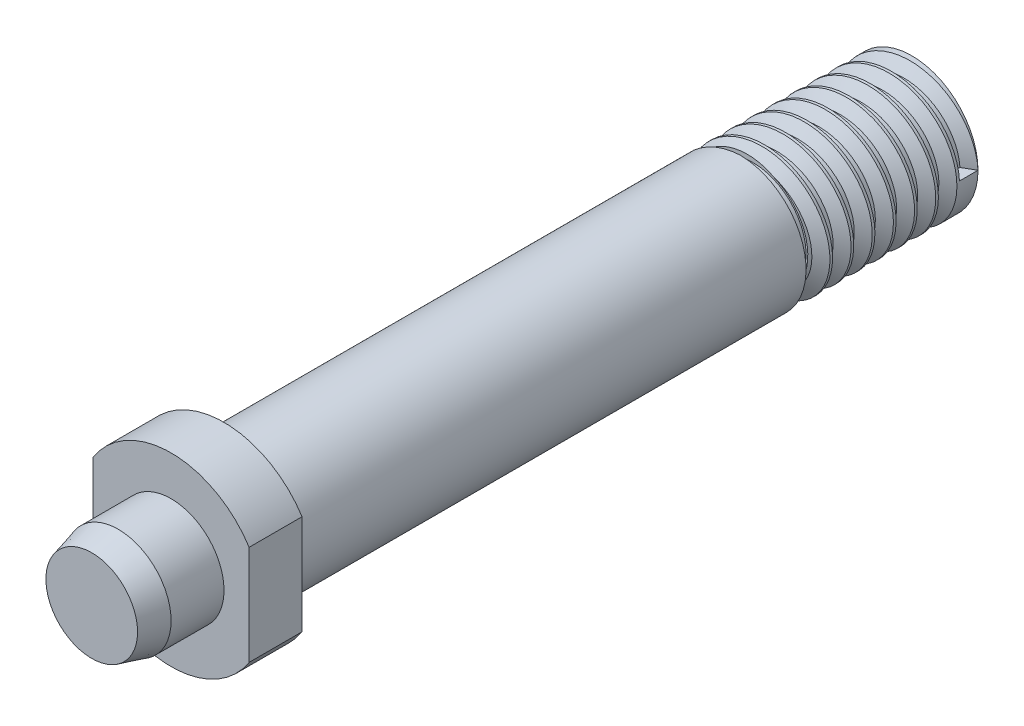
SolidWorks part; units mm, degrees
ref_plane "Front Plane" through (0, 0, 0) normal (0, 0, 1) x (1, 0, 0)
ref_plane "Top Plane" through (0, 0, 0) normal (0, 1, 0) x (1, 0, 0)
ref_plane "Right Plane" through (0, 0, 0) normal (1, 0, 0) x (0, 0, -1)
sketch "Sketch1" plane through (0, 0, 0) normal (0, 0, 1) x (1, 0, 0)
  circle A0 centre (0, 0) radius 2
  dimension "D1" = 4
extrude "Boss-Extrude1" add sketch "Sketch1" along normal blind 1 draft 15
sketch "Sketch2" plane through (0, 0, 0) normal (0, 0, -1) x (-1, 0, 0)
  circle A0 centre (0, 0) radius 2
extrude "Boss-Extrude2" add sketch "Sketch2" along normal blind 2
sketch "Sketch3" plane through (0, 0, -2) normal (0, 0, -1) x (-1, 0, 0)
  line L0 (-2.95, -1.8835) -> (-2.95, 1.8835)
  line L1 (2.95, -1.8835) -> (2.95, 1.8835)
  arc A0 (2.95, 1.8835) -> (-2.95, 1.8835) centre (0, 0) ccw
  arc A1 (-2.95, -1.8835) -> (2.95, -1.8835) centre (0, 0) ccw
  dimension "D1" = 7
  dimension "D2" = 5.9
extrude "Boss-Extrude3" add sketch "Sketch3" along normal blind 2
sketch "Sketch4" plane through (0, 0, -4) normal (0, 0, -1) x (-1, 0, 0)
  circle A0 centre (0, 0) radius 2.5
  dimension "D1" = 5
extrude "Boss-Extrude4" add sketch "Sketch4" along normal blind 19.5
sketch "Sketch5" plane through (0, 0, -23.5) normal (0, 0, -1) x (-1, 0, 0)
  circle A0 centre (0, 0) radius 2
  dimension "D1" = 4
extrude "Boss-Extrude5" add sketch "Sketch5" along normal blind 0.5
sketch "Sketch6" plane through (0, 0, -24) normal (0, 0, -1) x (-1, 0, 0)
  circle A0 centre (0, 0) radius 2.5
extrude "Boss-Extrude6" add sketch "Sketch6" along normal blind 6
thread "Thread1" pitch 0.8 method cut profile "Thread Profile1" start angle 0, offset 0, length 6, pitch 0.8, diameter 5
ref_plane "Plane1" through (2.5, 0, -30) normal (0, -1, 0) x (1, 0, 0)
sketch "Thread Profile1" plane through (2.5, 0, -30) normal (0, -1, 0) x (1, 0, 0)
  line L0 (0, 0) -> (0, 0.8) construction
  line L11 (0, 0) -> (0, 0.7)
  line L12 (0, 0.7) -> (-0.433, 0.45)
  line L13 (-0.433, 0.45) -> (-0.433, 0.25)
  line L15 (-0.433, 0.25) -> (0, 0)
  line L17 (-0.433, 0.35) -> (0, 0.35) construction
  point P2 (0, 0)
  dimension "Pitch" = 0.8
  dimension "Profile_Angle" = 60
  dimension "Profile_Land" = 0.2
  dimension "Profile_Height" = 0.433
